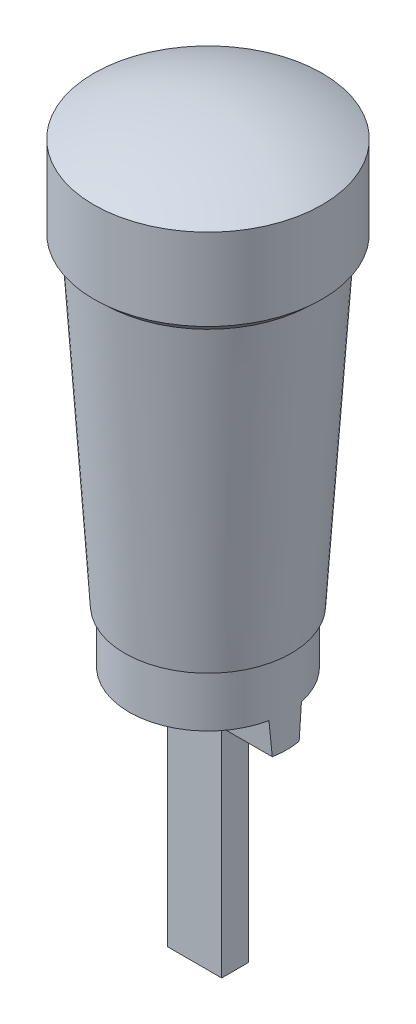
SolidWorks part; units mm, degrees
ref_plane "Front Plane" through (0, 0, 0) normal (0, 0, 1) x (1, 0, 0)
ref_plane "Top Plane" through (0, 0, 0) normal (0, 1, 0) x (1, 0, 0)
ref_plane "Right Plane" through (0, 0, 0) normal (1, 0, 0) x (0, 0, -1)
ref_plane "Plane1" through (0, 0, 0) normal (1, 0, 0) x (0, 0, -1)
sketch "Sketch1" plane through (0, 0, 0) normal (1, 0, 0) x (0, 0, -1)
  line L0 (5.3467, 29.6164) -> (5.3467, 25.7877)
  line L1 (5.3467, 25.7877) -> (4.8398, 25.316)
  line L2 (4.8398, 25.316) -> (3.899, 10.6934)
  line L3 (3.899, 10.6934) -> (3.6957, 10.6934)
  line L4 (3.6957, 10.6934) -> (3.6957, 6.2738)
  line L5 (3.6957, 6.2738) -> (0, 6.2738)
  line L6 (0, 6.2738) -> (0, 30.8864)
  line L7 (0, 6.2738) -> (0, 30.8864) construction
  arc A0 (0, 30.8864) -> (5.3467, 29.6164) centre (0, 18.9966) cw
revolve "Revolve1" add sketch "Sketch1" angle 360 about L7 reverse direction yes
ref_plane "Plane2" through (0, 0, 0) normal (1, 0, 0) x (0, 0, -1)
sketch "Sketch2" plane through (0, 0, 0) normal (1, 0, 0) x (0, 0, -1)
  line L0 (-3.6957, 5.1562) -> (3.6957, 5.1562)
  line L1 (3.6957, 5.1562) -> (3.6957, 8.2042)
  line L2 (3.6957, 8.2042) -> (0.762, 8.2042)
  line L3 (0.762, 8.2042) -> (0.6287, 6.6802)
  line L4 (0.6287, 6.6802) -> (-0.6287, 6.6802)
  line L5 (-0.6287, 6.6802) -> (-0.762, 8.2042)
  line L6 (-0.762, 8.2042) -> (-3.6957, 8.2042)
  line L7 (-3.6957, 8.2042) -> (-3.6957, 5.1562)
extrude "Cut-Extrude1" cut sketch "Sketch2" against normal blind 12 and the other way blind 12
ref_plane "Plane3" through (0, 0, 0) normal (1, 0, 0) x (0, 0, -1)
sketch "Sketch3" plane through (0, 0, 0) normal (1, 0, 0) x (0, 0, -1)
  line L0 (-0.6287, 6.6802) -> (-0.6287, -3.4798)
  line L1 (-0.6287, -3.4798) -> (0.6287, -3.4798)
  line L2 (0.6287, -3.4798) -> (0.6287, 6.6802)
  line L3 (0.6287, 6.6802) -> (-0.6287, 6.6802)
extrude "Boss-Extrude1" add sketch "Sketch3" against normal blind 1.27 and the other way blind 1.27
